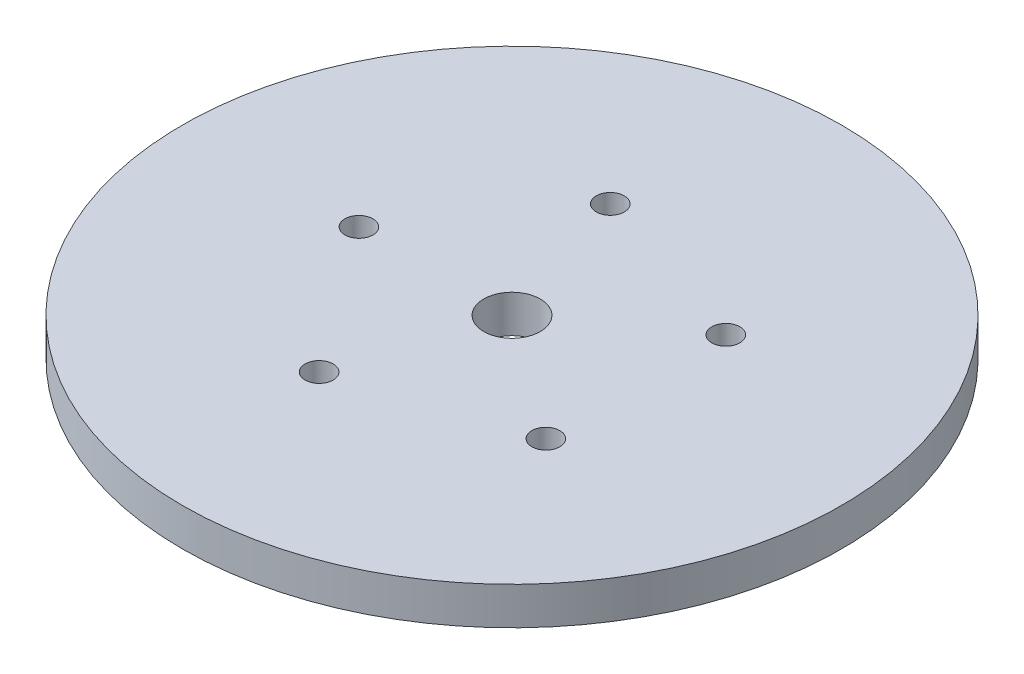
SolidWorks part; units mm, degrees
ref_plane "Front Plane" through (0, 0, 0) normal (0, 0, 1) x (1, 0, 0)
ref_plane "Top Plane" through (0, 0, 0) normal (0, 1, 0) x (1, 0, 0)
ref_plane "Right Plane" through (0, 0, 0) normal (1, 0, 0) x (0, 0, -1)
sketch "Sketch1" plane through (0, 0, 0) normal (0, 1, 0) x (1, 0, 0)
  circle A0 centre (0, 0) radius 87.5
  dimension "FLANGE_OD" = 175
extrude "Boss-Extrude1" add sketch "Sketch1" along normal blind 10
sketch "Sketch2" plane through (0, 0, 0) normal (0, 1, 0) x (1, 0, 0)
  circle A0 centre (0, 0) radius 7.5
  dimension "BORE_D" = 15
extrude "Cut-Extrude1" cut sketch "Sketch2" along normal through all
sketch "Sketch3" plane through (0, 10, 0) normal (0, 1, 0) x (1, 0, 0)
  circle A0 centre (0, 0) radius 40.6422 construction
  circle A1 centre (-40.6422, 0) radius 3.7216
  dimension "BOLT_D" = 7.4432
  dimension "BOLT_PCD" = 81.2844
extrude "Cut-Extrude2" cut sketch "Sketch3" against normal blind 8.414
pattern_circular "CirPattern1" count 5 over 360 about axis through (0, 0, 0) along (0, 1, 0) of "Cut-Extrude2"
